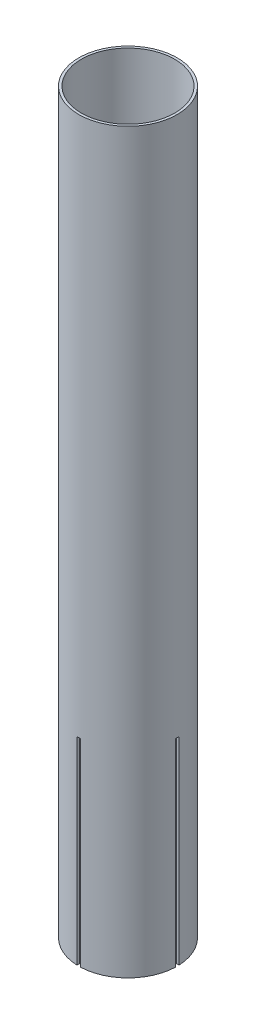
SolidWorks part; units mm, degrees
ref_plane "Front Plane" through (0, 0, 0) normal (0, 0, 1) x (1, 0, 0)
ref_plane "Top Plane" through (0, 0, 0) normal (0, 1, 0) x (1, 0, 0)
ref_plane "Right Plane" through (0, 0, 0) normal (1, 0, 0) x (0, 0, -1)
sketch "Sketch1" plane through (0, 0, 0) normal (0, 1, 0) x (1, 0, 0)
  circle A0 centre (0, 0) radius 38
  circle A1 centre (0, 0) radius 40
  dimension "D1" = 80
  dimension "D2" = 2
extrude "Boss-Extrude1" add sketch "Sketch1" along normal blind 600
sketch "Sketch2" plane through (0, 0, 0) normal (1, 0, 0) x (0, 0, -1)
  line L0 (-40, 0) -> (40, 0) construction
  line L1 (1.5, 161) -> (-1.5, 161)
  line L2 (1.5, 161) -> (1.5, 0)
  line L3 (1.5, 0) -> (-1.5, 0)
  line L4 (-1.5, 161) -> (-1.5, 0)
  line L5 (1.5, 161) -> (-1.5, 0) construction
  line L6 (1.5, 0) -> (-1.5, 161) construction
  point P0 (0, 80.5)
  dimension "D1" = 3
  dimension "D2" = 161
extrude "Cut-Extrude1" cut sketch "Sketch2" against normal through all
pattern_circular "CirPattern1" count 4 over 360 about axis through (0, 600, 0) along (0, -1, 0) of "Cut-Extrude1"
